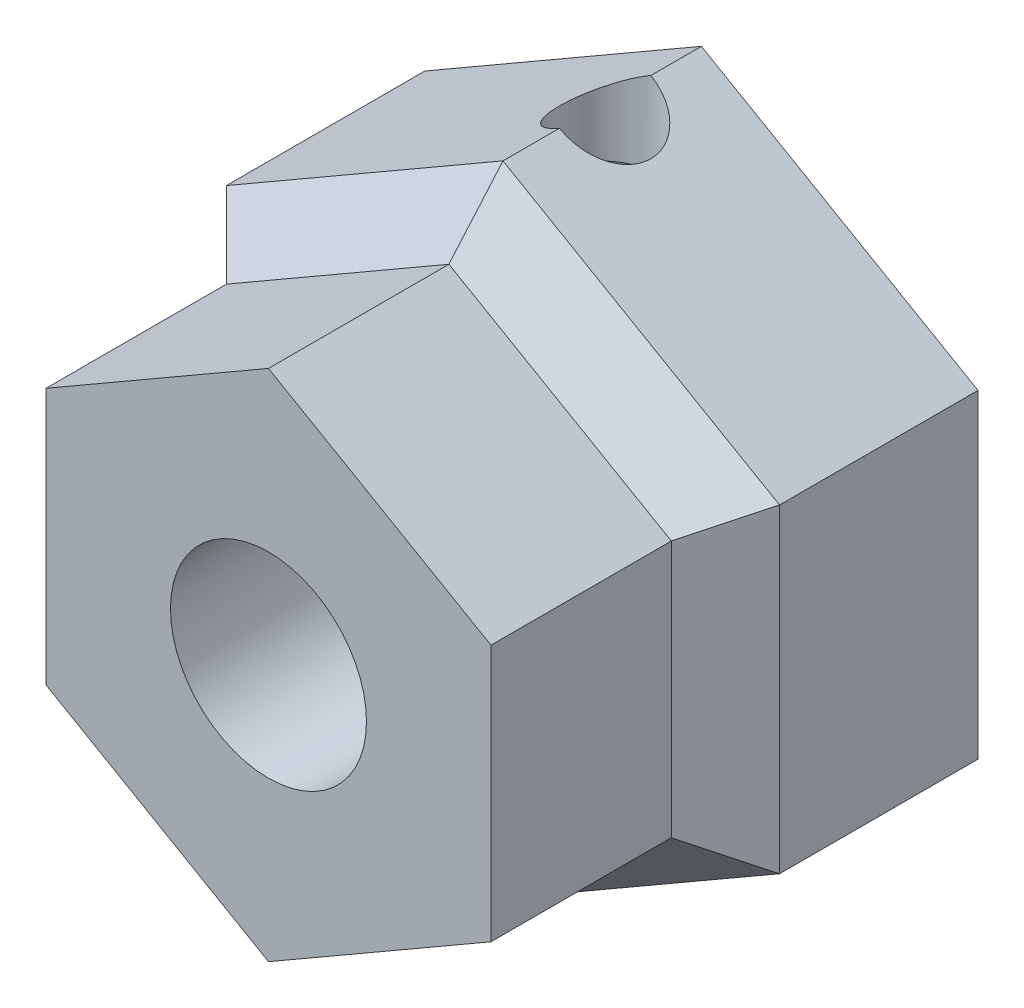
SolidWorks part; units mm, degrees
ref_plane "Front Plane" through (0, 0, 0) normal (0, 0, 1) x (1, 0, 0)
ref_plane "Top Plane" through (0, 0, 0) normal (0, 1, 0) x (1, 0, 0)
ref_plane "Right Plane" through (0, 0, 0) normal (1, 0, 0) x (0, 0, -1)
sketch "Sketch2" plane through (0, 0, 0) normal (0, 0, 1) x (1, 0, 0)
  line L1 (11.5, -6.6395) -> (11.5, 6.6395)
  line L2 (11.5, 6.6395) -> (0, 13.2791)
  line L3 (0, 13.2791) -> (-11.5, 6.6395)
  line L4 (-11.5, 6.6395) -> (-11.5, -6.6395)
  line L5 (-11.5, -6.6395) -> (0, -13.2791)
  line L6 (0, -13.2791) -> (11.5, -6.6395)
  circle A1 centre (0, 0) radius 4.075
  circle A2 centre (0, 0) radius 11.5 construction
  point P2 (-11.07, -3.2845)
  dimension "D1" = 8.15
  dimension "D3" = 23
extrude "Boss-Extrude2" add sketch "Sketch2" along normal blind 8
sketch "Sketch18" plane through (0, 0, 8) normal (0, 0, -1) x (-1, 0, 0)
  line L1 (0, -10.681) -> (9.25, -5.3405)
  line L2 (9.25, -5.3405) -> (9.25, 5.3405)
  line L3 (9.25, 5.3405) -> (0, 10.681)
  line L4 (0, 10.681) -> (-9.25, 5.3405)
  line L5 (-9.25, 5.3405) -> (-9.25, -5.3405)
  line L6 (-9.25, -5.3405) -> (0, -10.681)
  circle A0 centre (0, 0) radius 9.25 construction
  point P1 (-1.5105, -10.5736)
  circle M18 centre (0, 0) radius 4.075
  dimension "D1" = 18.5
extrude "Boss-Extrude4" add sketch "Sketch18" against normal blind 10 contours L6 L5 L4 L3 L2 L1 M18 region at (4.4837, -7.766, 8)
sketch "Sketch5" plane through (0, 0, 0) normal (0, -1, 0) x (0, 0, -1)
  circle A0 centre (-4, 0) radius 1.9
  dimension "D2" = 3.8
  dimension "D1" = 4
extrude "Cut-Extrude8" cut sketch "Sketch5" against normal through all
ref_plane "Plane3" through (0, 7, 0) normal (0, 1, 0) x (1, 0, 0)
sketch "Sketch16" plane through (0, 7, 0) normal (0, 1, 0) x (1, 0, 0)
  line L1 (0, -7.2909) -> (2.85, -5.6454)
  line L2 (2.85, -5.6454) -> (2.85, -2.3546)
  line L3 (2.85, -2.3546) -> (0, -0.7091) construction
  line L4 (0, -0.7091) -> (-2.85, -2.3546) construction
  line L5 (-2.85, -2.3546) -> (-2.85, -5.6454)
  line L6 (-2.85, -5.6454) -> (0, -7.2909)
  line L11 (-2.85, -2.3546) -> (2.85, -2.3546) construction
  line L12 (-2.85, -2.3546) -> (-2.85, 0)
  line L13 (-2.85, 0) -> (2.85, 0)
  line L14 (2.85, -2.3546) -> (2.85, 0)
  line L15 (11.5, 0) -> (0, 0) construction
  circle A0 centre (0, -4) radius 2.85 construction
  point P9 (0, 0)
  point P11 (2.85, 0.8943)
  dimension "D1" = 5.7
  dimension "D2" = 4
extrude "Cut-Extrude7" cut sketch "Sketch16" along normal blind 2.8
pattern_circular "CirPattern1" count 2 every 90 about axis through (0, 0, 0) along (0, 0, 1) of "Cut-Extrude7", "Cut-Extrude8"
sketch "Sketch17" plane through (0, 0, 0) normal (0, 0, -1) x (-1, 0, 0)
  circle A0 centre (0, 0) radius 5.575
  circle A1 centre (0, 0) radius 4.075
  circle A3 centre (0, 0) radius 4.075 construction
  dimension "D1" = 1.5
extrude "Boss-Extrude3" add sketch "Sketch17" along normal blind 2.5
chamfer "Chamfer4" distance 2.5 angle 45 6 edges at (4.625, -8.0107, 8) (-4.625, -8.0107, 8) (-9.25, 0, 8) (-4.625, 8.0107, 8) (4.625, 8.0107, 8) (9.25, 0, 8)
